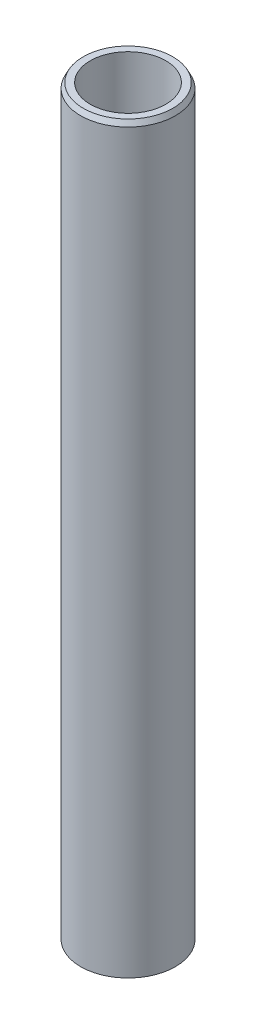
SolidWorks part; units mm, degrees
ref_plane "Front Plane" through (0, 0, 0) normal (0, 0, 1) x (1, 0, 0)
ref_plane "Top Plane" through (0, 0, 0) normal (0, 1, 0) x (1, 0, 0)
ref_plane "Right Plane" through (0, 0, 0) normal (1, 0, 0) x (0, 0, -1)
sketch "Sketch1" plane through (0, 0, 0) normal (0, 1, 0) x (1, 0, 0)
  circle A0 centre (0, 0) radius 30
  dimension "SHAFT_OD" = 60
extrude "Boss-Extrude1" add sketch "Sketch1" along normal blind 471.5717
sketch "Sketch2" plane through (0, 0, 0) normal (0, 1, 0) x (1, 0, 0)
  circle A0 centre (0, 0) radius 23.9171
  dimension "BORE_D" = 47.8342
extrude "Cut-Extrude1" cut sketch "Sketch2" along normal through all
chamfer "Chamfer1" distance 3.237 angle 27.165 2 edges at (0, 471.5717, 30) (0, 0, 30) first distance on face at (0, 471.5717, 30) first distance on face at (0, 0, 23.9171)
